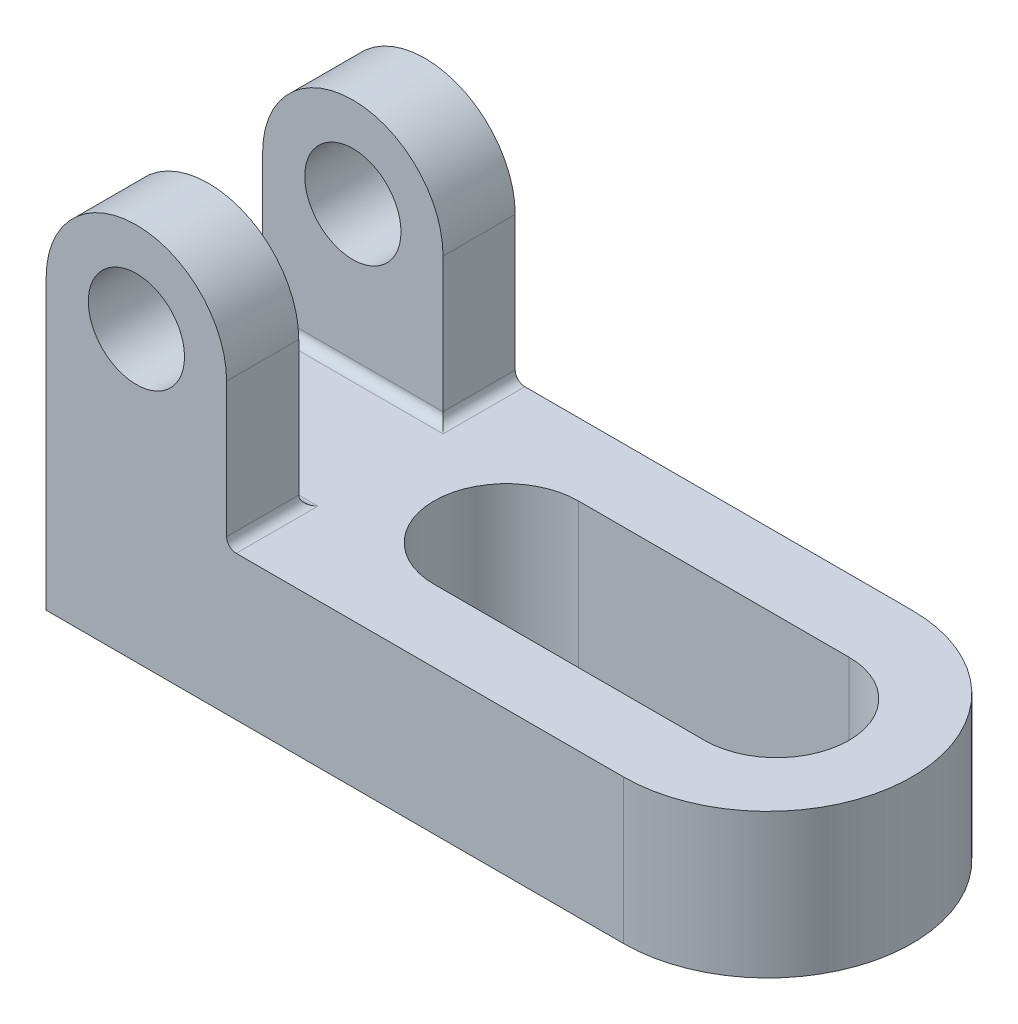
SolidWorks part; units mm, degrees
material "Thornel Mat VMA"
ref_plane "Front Plane" through (0, 0, 0) normal (0, 0, 1) x (1, 0, 0)
ref_plane "Top Plane" through (0, 0, 0) normal (0, 1, 0) x (1, 0, 0)
ref_plane "Right Plane" through (0, 0, 0) normal (1, 0, 0) x (0, 0, -1)
sketch "Sketch1" plane through (0, 0, 0) normal (0, 0, 1) x (1, 0, 0)
  line L2 (75, 0) -> (75, -30)
  line L3 (75, -30) -> (-75, -30)
  line L4 (-75, 30) -> (-75, -30)
  line L8 (-37.5, 0) -> (75, 0)
  line L9 (-37.5, 0) -> (-37.5, 30)
  arc A0 (-75, 30) -> (-37.5, 30) centre (-56.25, 30) cw
  circle A1 centre (-56.25, 30) radius 10
  point P1 (0, 0)
  dimension "D6" = 18.75
  dimension "D7" = 20
  dimension "D1" = 150
  dimension "D2" = 75
  dimension "D3" = 37.5
  dimension "D4" = 30
  dimension "D5" = 60
extrude "Boss-Extrude1" add sketch "Sketch1" against normal blind 60
sketch "Sketch3" plane through (0, 0, 0) normal (0, 1, 0) x (1, 0, 0)
  line L1 (-75, 60) -> (-75, 0) construction
  line L2 (-75, 45) -> (-75, 15)
  line L4 (-75, 45) -> (-37.5, 45)
  line L5 (-37.5, 60) -> (-37.5, 0) construction
  line L6 (-37.5, 45) -> (-37.5, 15)
  line L7 (-37.5, 15) -> (-75, 15)
  line L15 (46.875, 15) -> (-9.375, 15)
  line L16 (46.875, 45) -> (-9.375, 45)
  arc A0 (46.875, 15) -> (46.875, 45) centre (46.875, 30) ccw
  arc A1 (-9.375, 45) -> (-9.375, 15) centre (-9.375, 30) ccw
  point P24 (18.75, 30)
  dimension "D2" = 30
extrude "Cut-Extrude1" cut sketch "Sketch3" along normal through all contours L2 L7 L6 L4
extrude "Cut-Extrude2" cut sketch "Sketch3<5>" against normal through all contours L16 A1 L15 A0 region at (18.75, 0, -30)
sketch "Sketch3<5>" plane through (0, 0, 0) normal (0, 1, 0) x (1, 0, 0) same geometry as "Sketch3"
fillet "Fillet1" 2 edges at (75, -15, 0) (75, -15, -60) type full round first side face at (-46.25, 30, 0) second side face at (-46.25, 30, -60) middle face at (75, -15, -30)
fillet "Fillet2" radius 2 4 edges at (-56.25, 0, -15) (-56.25, 0, -45) (-37.5, 0, -52.5) (-37.5, 0, -7.5)
